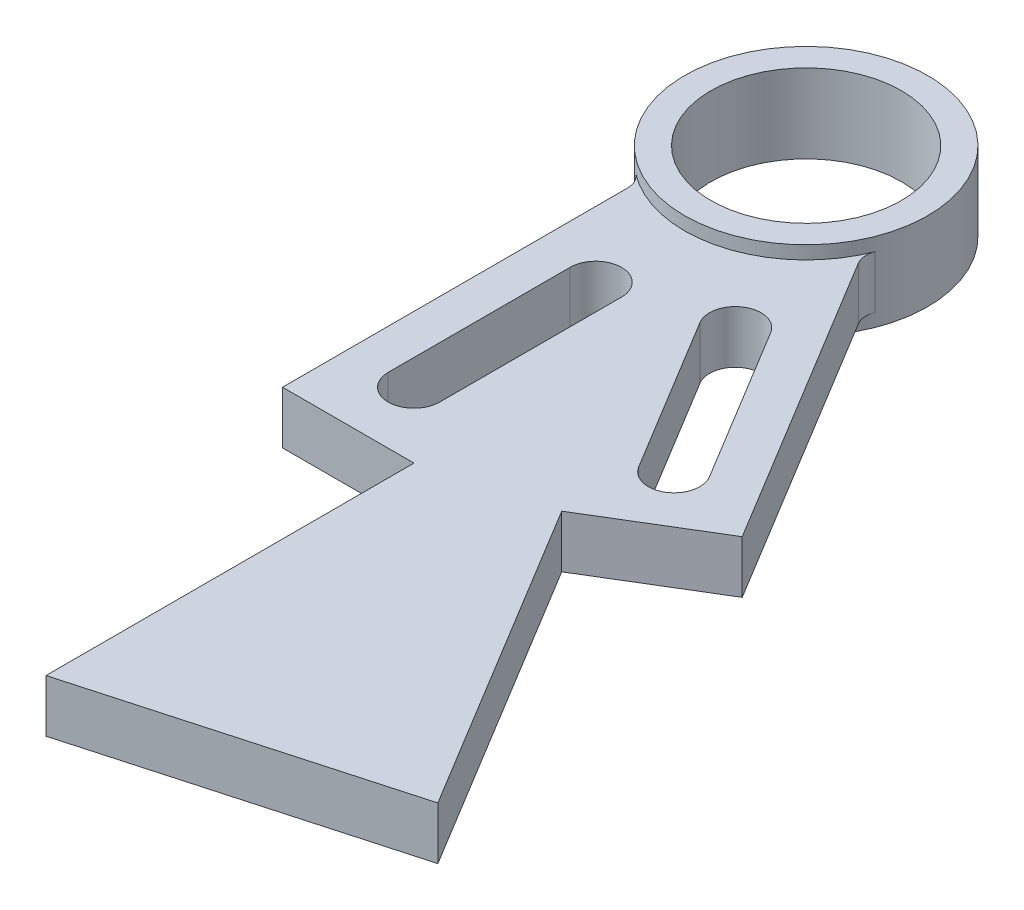
SolidWorks part; units mm, degrees
material "AISI 4130 Steel, annealed at 865C"
ref_plane "Front Plane" through (0, 0, 0) normal (0, 0, 1) x (1, 0, 0)
ref_plane "Top Plane" through (0, 0, 0) normal (0, 1, 0) x (1, 0, 0)
ref_plane "Right Plane" through (0, 0, 0) normal (1, 0, 0) x (0, 0, -1)
sketch "Sketch1" plane through (0, 0, 0) normal (0, 1, 0) x (1, 0, 0)
  line L0 (0, -50.4952) -> (0, -14.6812) construction
  line L1 (26.1781, -43.1795) -> (7.6111, -12.5542) construction
  line L2 (0, -47.3837) -> (0, -25.4127) construction
  line L5 (-3.1115, -47.3837) -> (-3.1115, -25.4127)
  line L8 (-7.9375, -55.3212) -> (7.9375, -55.3212)
  line L9 (21.8925, -51.4214) -> (35.4676, -43.1913)
  line L10 (-7.9375, -55.3212) -> (-7.9375, -12.3505)
  line L11 (35.4676, -43.1913) -> (13.1903, -6.4461)
  line L12 (7.9375, -55.3212) -> (7.9375, -99.7712)
  line L13 (21.8925, -51.4214) -> (44.9366, -89.4315)
  line L14 (7.9375, -99.7712) -> (44.9366, -89.4315)
  line L15 (0, -14.6812) -> (0, 0) construction
  line L16 (0, -55.3212) -> (0, -50.4952) construction
  line L17 (28.6801, -47.3063) -> (26.1781, -43.1795)
  line L18 (3.1115, -47.3837) -> (3.1115, -25.4127)
  line L19 (13.1747, -21.7309) -> (24.565, -40.5188) construction
  line L20 (15.8354, -20.1179) -> (27.2257, -38.9057)
  line L21 (10.5139, -23.344) -> (21.9043, -42.1319)
  line L22 (7.6111, -12.5542) -> (0, 0) construction
  line L23 (0, 0) -> (20.5089, -73.3882) construction
  line L25 (184.8058, -304.8281) -> (14.725, -24.2882) construction
  line L27 (0, 0) -> (26.4371, -94.6014) construction
  circle A0 centre (0, 0) radius 11.5062
  circle A1 centre (0, 0) radius 14.6812
  arc A2 (-3.1115, -47.3837) -> (3.1115, -47.3837) centre (0, -47.3837) ccw
  arc A3 (3.1115, -25.4127) -> (-3.1115, -25.4127) centre (0, -25.4127) ccw
  arc A4 (15.8354, -20.1179) -> (10.5139, -23.344) centre (13.1747, -21.7309) ccw
  arc A5 (21.9043, -42.1319) -> (27.2257, -38.9057) centre (24.565, -40.5188) ccw
  point P9 (0, -36.3982)
  point P14 (18.8698, -31.1249)
  point P23 (0, -55.3212)
  point P26 (28.6801, -47.3063)
  point P33 (0, -50.4952)
  point P36 (26.1781, -43.1795)
  point P38 (0, -22.3012)
  dimension "D2" = 29.3624
  dimension "D3" = 40.64
  dimension "D4" = 4.826
  dimension "D6" = 44.45
  dimension "D7" = 7.9375
  dimension "D5" = 4.826
  dimension "D8" = 7.62
  dimension "D9" = 76.2
extrude "Bearing extrude" add sketch "Sketch1" along normal mid plane 9.525 contours A1 A0 region at (-6.8368, 0, -12.521)
extrude "Boss-Extrude2" add sketch "Sketch1<5>" along normal mid plane 6.35 contours A1 L10 L8 L12 L14 L13 L9 L11 A4 A2 region at (15.6772, 0, 56.0987)
sketch "Sketch1<5>" plane through (0, 0, 0) normal (0, 1, 0) x (1, 0, 0) same geometry as "Sketch1"
sketch3d "Tab Point"
  line L0 (20.5089, 0, 73.3882) -> (20.5089, 22.225, 73.3882) construction
  line L1 (0, 0, 0) -> (20.5089, 0, 73.3882) construction
  line L2 (0, 0, 0) -> (26.4371, 0, 94.6014) construction
  dimension "D1" = 22.225
fillet "Fillet1" radius 2.54 2 edges at (13.1903, 0, 6.4461) (-7.9375, 0, 12.3505)
equation "\"Apex_thickness\"= .25"
equation "\"Bearing_diameter\"= .906"
equation "\"A-arm_angle\"= 32.91"
equation "\"D1@Sketch1\"=\"Bearing_diameter\""
equation "\"D1@Boss-Extrude2\"= \"Apex_thickness\""
equation "\"apex slot\"= 1.4"
equation "\"tube diameter\"= 5 / 8"
